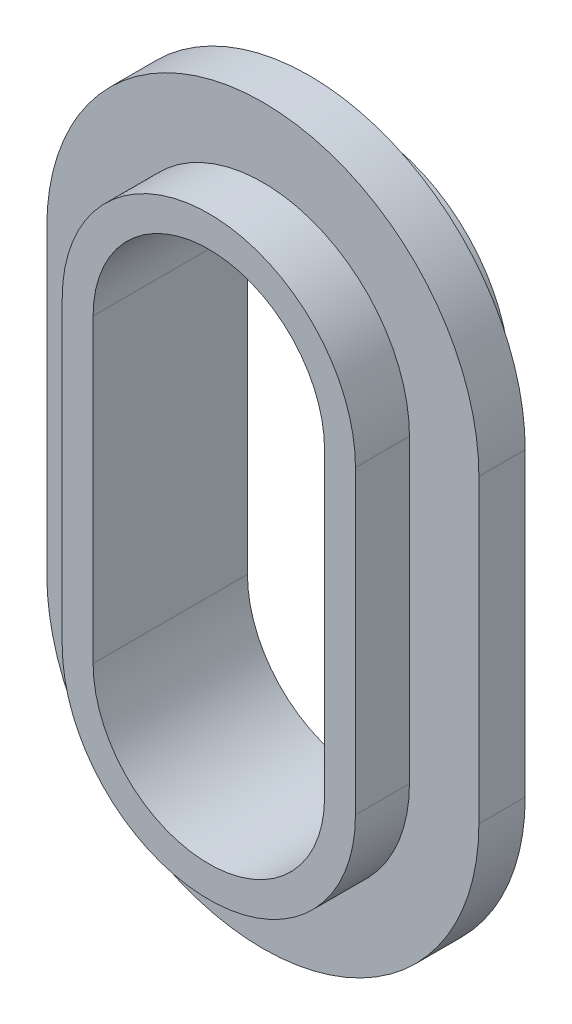
SolidWorks part; units mm, degrees
ref_plane "Top Plane" through (0, 0, 0) normal (0, 0, 1) x (1, 0, 0)
ref_plane "Front Plane" through (0, 0, 0) normal (0, 1, 0) x (1, 0, 0)
ref_plane "Right Plane" through (0, 0, 0) normal (1, 0, 0) x (0, 0, -1)
sketch "Sketch1" plane through (0, 0, 0) normal (0, 0, 1) x (1, 0, 0)
  line L0 (0, 0) -> (0, -7.8) construction
  line L1 (3.8, 0) -> (3.8, -7.8)
  line L2 (-3.8, 0) -> (-3.8, -7.8)
  line L3 (0, 0) -> (0, -7.8) construction
  line L4 (5.6, 0) -> (5.6, -7.8)
  line L5 (-5.6, 0) -> (-5.6, -7.8)
  line L6 (0, 0) -> (0, -7.8) construction
  line L7 (3, 0) -> (3, -7.8)
  line L8 (-3, 0) -> (-3, -7.8)
  arc A0 (3.8, 0) -> (-3.8, 0) centre (0, 0) ccw
  arc A1 (-3.8, -7.8) -> (3.8, -7.8) centre (0, -7.8) ccw
  arc A2 (5.6, 0) -> (-5.6, 0) centre (0, 0) ccw
  arc A3 (-5.6, -7.8) -> (5.6, -7.8) centre (0, -7.8) ccw
  arc A4 (3, 0) -> (-3, 0) centre (0, 0) ccw
  arc A5 (-3, -7.8) -> (3, -7.8) centre (0, -7.8) ccw
  point P3 (0, -3.9)
  point P8 (0, -3.9)
  point P17 (0, -3.9)
  dimension "D1" = 0.8
  dimension "D2" = 5.6
  dimension "D4" = 3
  dimension "D3" = 7.8
extrude "Boss-Extrude1" add sketch "Sketch1" along normal blind 0.6 and the other way blind 0.6 contours L2 A1 L1 A0 | L5 A3 L4 A2 A1 L2 A0 L1 region at (3.6283, -3.9, 0) region at (5.3794, -3.9, 0)
extrude "Boss-Extrude2" add sketch "Sketch1<3>" along normal blind 2 and the other way blind 2 contours A0 L2 A1 L1
sketch "Sketch1<3>" plane through (0, 0, 0) normal (0, 0, 1) x (1, 0, 0) same geometry as "Sketch1"
extrude "Cut-Extrude1" cut sketch "Sketch1<4>" against normal through all both and the other way through all contours A4 L8 A5 L7
sketch "Sketch1<4>" plane through (0, 0, 0) normal (0, 0, 1) x (1, 0, 0) same geometry as "Sketch1"
